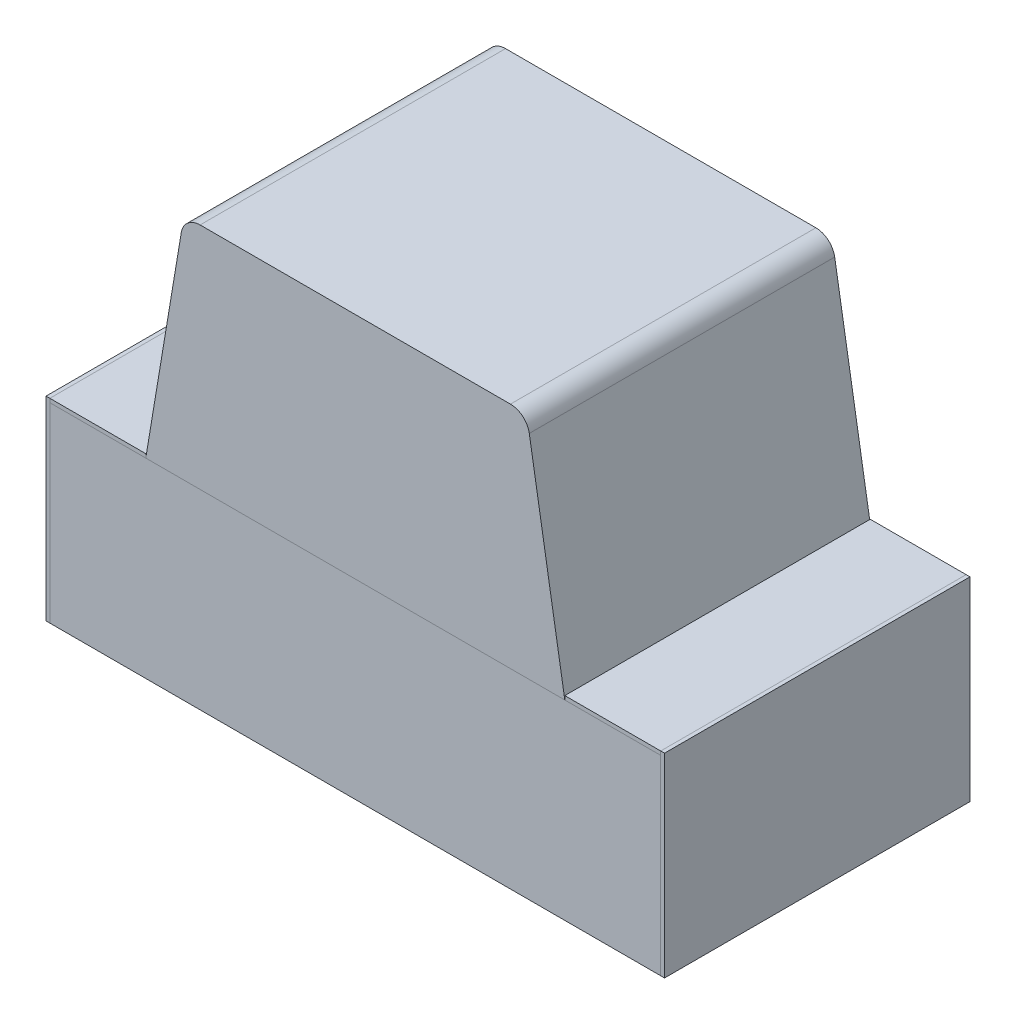
SolidWorks part; units mm, degrees
ref_plane "Płaszczyzna przednia" through (0, 0, 0) normal (0, 0, 1) x (1, 0, 0)
ref_plane "Płaszczyzna górna" through (0, 0, 0) normal (0, 1, 0) x (1, 0, 0)
ref_plane "Płaszczyzna prawa" through (0, 0, 0) normal (1, 0, 0) x (0, 0, -1)
sketch "Szkic2" plane through (0, 0, 0) normal (0, 1, 0) x (1, 0, 0)
  line L1 (0.8, -0.4) -> (-0.8, -0.4)
  line L2 (0.8, -0.4) -> (0.8, 0.4)
  line L3 (0.8, 0.4) -> (-0.8, 0.4)
  line L4 (-0.8, -0.4) -> (-0.8, 0.4)
  line L5 (0.8, -0.4) -> (-0.8, 0.4) construction
  line L6 (0.8, 0.4) -> (-0.8, -0.4) construction
  point P1 (0, 0)
  dimension "D1" = 0.8
  dimension "D2" = 1.6
extrude "Dodanie-wyciągnięcie1" add sketch "Szkic2" along normal blind 0.5
sketch "Szkic6" plane through (0, 0.5, 0) normal (0, 1, 0) x (1, 0, 0)
  line L0 (0.8, 0.4) -> (-0.8, 0.4) construction
  line L1 (0.5488, -0.4) -> (-0.5488, -0.4)
  line L2 (0.5488, -0.4) -> (0.5488, 0.4)
  line L3 (0.5488, 0.4) -> (-0.5488, 0.4)
  line L4 (-0.5488, -0.4) -> (-0.5488, 0.4)
  line L5 (0.5488, -0.4) -> (-0.5488, 0.4) construction
  line L6 (0.5488, 0.4) -> (-0.5488, -0.4) construction
  point P0 (0, 0)
extrude "Dodanie-wyciągnięcie4" add sketch "Szkic6" along normal blind 0.6 separate body
sketch "Szkic7" plane through (0, 0.5, 0) normal (0, 1, 0) x (1, 0, 0)
  line L1 (0.1141, -0.1339) -> (0.3772, -0.1339)
  line L2 (0.1141, -0.1339) -> (0.1141, 0.1339)
  line L3 (0.1141, 0.1339) -> (0.3772, 0.1339)
  line L4 (0.3772, -0.1339) -> (0.3772, 0.1339)
  line L5 (0.1141, -0.1339) -> (0.3772, 0.1339) construction
  line L6 (0.1141, 0.1339) -> (0.3772, -0.1339) construction
  point P0 (0.2456, 0)
extrude "Dodanie-wyciągnięcie5" add sketch "Szkic7" along normal blind 0.12 separate body
chamfer "Sfazowanie3" distance 0.6 distance2 0.1 1 edges at (-0.5488, 1.1, 0) first distance on face at (-0.5488, 0.8, 0)
chamfer "Sfazowanie4" distance 0.6 distance2 0.1 1 edges at (0.5488, 1.1, 0) first distance on face at (0.5488, 0.8, 0)
fillet "Zaokrąglenie3" radius 0.05 1 edges at (0.4488, 1.1, 0)
fillet "Zaokrąglenie4" radius 0.05 1 edges at (-0.4488, 1.1, 0)
sketch "Szkic8" plane through (0, 0.5, 0) normal (0, 1, 0) x (1, 0, 0)
  line L1 (-0.8, -0.4) -> (-0.5488, -0.4)
  line L2 (-0.8, -0.4) -> (-0.8, 0.4)
  line L3 (-0.8, 0.4) -> (-0.5488, 0.4)
  line L4 (-0.5488, -0.4) -> (-0.5488, 0.4)
  line L5 (0.5488, 0.4) -> (0.8, 0.4)
  line L6 (0.5488, 0.4) -> (0.5488, -0.4)
  line L7 (0.5488, -0.4) -> (0.8, -0.4)
  line L8 (0.8, 0.4) -> (0.8, -0.4)
extrude "Dodanie-wyciągnięcie6" add sketch "Szkic8" along normal blind 0.01 separate body
sketch "Szkic9" plane through (-0.8, 0, 0) normal (-1, 0, 0) x (0, 0, 1)
  line L1 (0.4, 0) -> (-0.4, 0)
  line L2 (0.4, 0) -> (0.4, 0.51)
  line L3 (0.4, 0.51) -> (-0.4, 0.51)
  line L4 (-0.4, 0) -> (-0.4, 0.51)
extrude "Dodanie-wyciągnięcie7" add sketch "Szkic9" along normal blind 0.01 separate body
sketch "Szkic10" plane through (0.8, 0, 0) normal (1, 0, 0) x (0, 0, -1)
  line L0 (-0.4, 0) -> (0.4, 0) construction
  line L1 (-0.4, 0.51) -> (0.4, 0.51)
  line L2 (-0.4, 0.51) -> (-0.4, 0)
  line L3 (-0.4, 0) -> (0.4, 0)
  line L4 (0.4, 0.51) -> (0.4, 0)
extrude "Dodanie-wyciągnięcie8" add sketch "Szkic10" along normal blind 0.01 separate body
fillet "Zaokrąglenie5" radius 0.03 4 edges at (0.2456, 0.62, 0.1339) (0.1141, 0.62, 0) (0.2456, 0.62, -0.1339) (0.3772, 0.62, 0)
